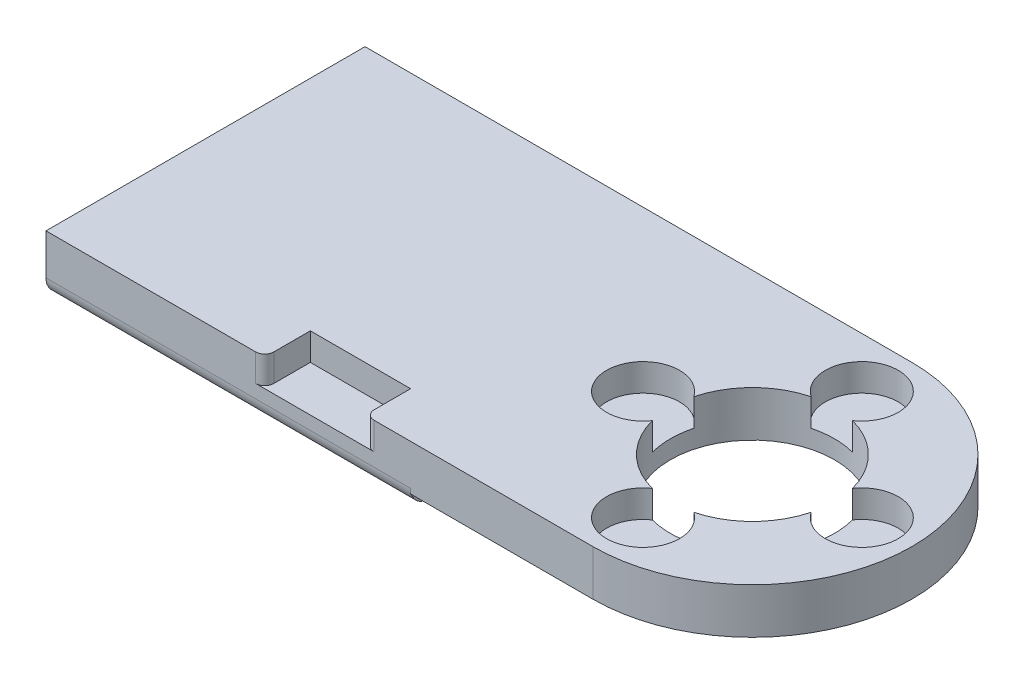
SolidWorks part; units mm, degrees
material "PEI"
ref_plane "Front Plane" through (0, 0, 0) normal (0, 0, 1) x (1, 0, 0)
ref_plane "Top Plane" through (0, 0, 0) normal (0, 1, 0) x (1, 0, 0)
ref_plane "Right Plane" through (0, 0, 0) normal (1, 0, 0) x (0, 0, -1)
sketch "Sketch1" plane through (0, 0, 0) normal (0, 1, 0) x (1, 0, 0)
  line L1 (20, -17.5) -> (-20, -17.5)
  line L2 (20, -17.5) -> (20, 17.5)
  line L3 (20, 17.5) -> (-20, 17.5)
  line L4 (-20, -17.5) -> (-20, 17.5)
  line L5 (20, -17.5) -> (-20, 17.5) construction
  line L6 (20, 17.5) -> (-20, -17.5) construction
  point P0 (0, 0)
  dimension "D1" = 35
  dimension "D2" = 40
extrude "Boss-Extrude1" add sketch "Sketch1" against normal blind 8
sketch "Sketch2" plane through (20, 0, 0) normal (1, 0, 0) x (0, 0, -1)
  line L0 (-17.5, -8) -> (-12.5, -5)
  line L1 (-12.5, -5) -> (12.5, -5)
  line L2 (0, -5) -> (0, -8)
  line L3 (17.5, -8) -> (12.5, -5)
  line L4 (17.5, 0) -> (-17.5, 0)
  line L5 (-17.5, 0) -> (-17.5, -8)
  line L6 (-17.5, -8) -> (17.5, -8)
  line L7 (17.5, -8) -> (17.5, 0)
  line L8 (17.5, 0) -> (-17.5, 0)
  line L9 (-17.5, 0) -> (-17.5, -8)
  line L10 (-17.5, -8) -> (17.5, -8)
  line L11 (17.5, -8) -> (17.5, 0)
  line M7 (-17.5, -8) -> (17.5, -8)
  dimension "D2" = 5
  dimension "D3" = 3
  dimension "D1" = 0
extrude "Cut-Extrude1" cut sketch "Sketch2" against normal through all and the other way through all contours L2 L1 L0 M7 | L3 L1 L2 M7 region at (20, -6.5833, 7.5694) region at (20, -6.5833, -7.5694)
fillet "Fillet1" radius 2 4 edges at (0, -5, 12.5) (0, -5, -12.5) (0, -8, -17.5) (0, -8, 17.5)
sketch "Sketch5" plane through (-20, 0, 0) normal (-1, 0, 0) x (0, 0, 1)
  line L1 (-17.5, 0) -> (17.5, 0)
  line L2 (-17.5, 0) -> (-17.5, -2)
  line L3 (-17.5, -2) -> (17.5, -2)
  line L4 (17.5, 0) -> (17.5, -2)
  line L6 (-17.5, 0) -> (-17.5, -4.4676)
  line L7 (-14.471, -6.1826) -> (-12.975, -5.285)
  line L8 (-11.946, -5) -> (11.946, -5)
  line L9 (12.975, -5.285) -> (14.471, -6.1826)
  line L10 (17.5, -4.4676) -> (17.5, 0)
  line L11 (17.5, 0) -> (-17.5, 0)
  line L12 (-17.5, 0) -> (-17.5, -4.4676)
  line L13 (-14.471, -6.1826) -> (-12.975, -5.285)
  line L14 (-11.946, -5) -> (11.946, -5)
  line L15 (12.975, -5.285) -> (14.471, -6.1826)
  line L16 (17.5, -4.4676) -> (17.5, 0)
  line L22 (17.5, 0) -> (-17.5, 0)
  arc A4 (-17.5, -4.4676) -> (-14.471, -6.1826) centre (-15.5, -4.4676) ccw
  arc A5 (-17.5, -4.4676) -> (-14.471, -6.1826) centre (-15.5, -4.4676) ccw
  arc A6 (-11.946, -5) -> (-12.975, -5.285) centre (-11.946, -7) ccw
  arc A7 (-11.946, -5) -> (-12.975, -5.285) centre (-11.946, -7) ccw
  arc A12 (12.975, -5.285) -> (11.946, -5) centre (11.946, -7) ccw
  arc A13 (12.975, -5.285) -> (11.946, -5) centre (11.946, -7) ccw
  arc A14 (14.471, -6.1826) -> (17.5, -4.4676) centre (15.5, -4.4676) ccw
  arc A15 (14.471, -6.1826) -> (17.5, -4.4676) centre (15.5, -4.4676) ccw
  dimension "D2" = 2
  dimension "D1" = 0
sketch "Sketch6" plane through (0, 0, 0) normal (0, 1, 0) x (1, 0, 0)
  line L0 (0, 0) -> (40, 0)
  line L1 (20, 17.5) -> (40, 17.5)
  line L2 (20, -17.5) -> (40, -17.5)
  line L4 (-20, 17.5) -> (-20, -17.5)
  line L5 (-20, -17.5) -> (20, -17.5)
  line L6 (20, -17.5) -> (20, 17.5)
  line L7 (20, 17.5) -> (-20, 17.5)
  line L8 (-20, 17.5) -> (-20, -17.5)
  line L9 (-20, -17.5) -> (20, -17.5)
  line L10 (20, -17.5) -> (20, 17.5)
  line L11 (20, 17.5) -> (-20, 17.5)
  circle A0 centre (40, 12) radius 4
  circle A2 centre (40, 0) radius 17.5
  circle A4 centre (40, 0) radius 12
  circle A5 centre (52, 0) radius 4
  circle A7 centre (40, 0) radius 9
  circle A13 centre (40, -12) radius 4
  circle A14 centre (28, 0) radius 4
  point P8 (28, 0)
  line M19 (20, -17.5) -> (20, 17.5)
  dimension "D3" = 8
  dimension "D4" = 8
  dimension "D5" = 8
  dimension "D6" = 8
  dimension "D7" = 24
  dimension "D8" = 18
  dimension "D2" = 40
  dimension "D1" = 0
extrude "Boss-Extrude2" add sketch "Sketch6" against normal up to surface (5 mm away) contours A2 L1 L0 M19 | A2 L0 L2 M19 | A14 A4 A0 A5 A13 A2 | A4 A0 | A0 A4 | A4 A14 L0 | L0 A14 A4 | A4 A14 L0 | L0 A14 A4 | A14 A4 A13 A5 A0 | A4 A13 | A4 A13 | A4 A5 | A4 A5 | A13 A4 A5 A7 | A14 A4 A13 A7 | A7 A5 A4 A0 | A14 A7 A0 A4 region at (24.3472, 0, -11.6563) region at (24.3472, 0, 11.6563) region at (26.4281, 0, -1.7834) region at (26.4281, 0, 1.7834) region at (27.9756, 0, -12.0244) region at (29.5619, 0, -1.7108) region at (29.5619, 0, 1.7108) region at (32.8149, 0, -7.1851) region at (32.8149, 0, 7.1851) region at (40, 0, -10.4381) region at (40, 0, -13.5719) region at (33.8102, 0, -6.1898) region at (40, 0, 10.4381) region at (40, 0, 13.5719) region at (47.1851, 0, -7.1851) region at (47.1851, 0, 7.1851) region at (53.5719, 0, 0) region at (50.4381, 0, 0) up to face at (0, -5, 0)
extrude "Cut-Extrude2" cut sketch "Sketch6<6>" against normal through all contours A14 A7 A13 A5 A0 | A5 A7 | A7 A13 | A7 A14 L0 | L0 A14 A7 | A0 A7 region at (31.4612, 0, -0.8606) region at (31.4612, 0, 0.8606) region at (33.8102, 0, -6.1898) region at (40, 0, -8.5388) region at (40, 0, 8.5388) region at (48.5388, 0, 0)
sketch "Sketch6<6>" plane through (0, 0, 0) normal (0, 1, 0) x (1, 0, 0) same geometry as "Sketch6"
extrude "Cut-Extrude3" cut sketch "Sketch6<7>" against normal blind 3 contours A4 A13 | A4 A5 | A4 A0 | A4 A14 L0 | L0 A14 A4 | A7 A5 A4 | A4 A13 A7 | A7 A14 A4 L0 | A4 A14 A7 L0 | A7 A0 A4 region at (26.4281, 0, -1.7834) region at (26.4281, 0, 1.7834) region at (29.5619, 0, -1.7108) region at (29.5619, 0, 1.7108) region at (40, 0, -10.4381) region at (40, 0, -13.5719) region at (40, 0, 10.4381) region at (40, 0, 13.5719) region at (53.5719, 0, 0) region at (50.4381, 0, 0)
sketch "Sketch6<7>" plane through (0, 0, 0) normal (0, 1, 0) x (1, 0, 0) same geometry as "Sketch6"
sketch "Sketch7" plane through (0, 0, 0) normal (0, 1, 0) x (1, 0, 0)
  line L0 (4, -17.5) -> (4, -12.5)
  line L1 (4, -12.5) -> (15, -12.5)
  line L2 (15, -12.5) -> (15, -17.5)
  line L3 (-20, 17.5) -> (-20, -17.5)
  line L4 (-20, -17.5) -> (40, -17.5)
  line L5 (40, 17.5) -> (-20, 17.5)
  line L6 (-20, 17.5) -> (-20, -17.5)
  line L7 (-20, -17.5) -> (40, -17.5)
  line L8 (40, 17.5) -> (-20, 17.5)
  arc A1 (40, -17.5) -> (40, 17.5) centre (40, 0) ccw
  arc A2 (40, -17.5) -> (40, 17.5) centre (40, 0) ccw
  line M17 (-20, -17.5) -> (40, -17.5)
  dimension "D2" = 11
  dimension "D3" = 5
  dimension "D4" = 24
  dimension "D1" = 0
extrude "Cut-Extrude4" cut sketch "Sketch7" against normal blind 3 contours L2 L1 L0 M17 region at (9.5, 0, 15)
fillet "Fillet2" radius 1 2 edges at (15, -1.5, 17.5) (4, -1.5, 17.5)
